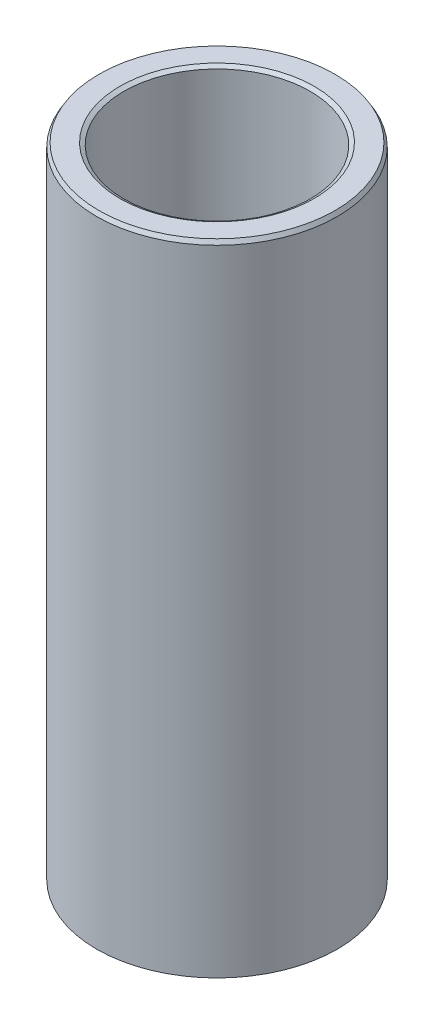
SolidWorks part; units mm, degrees
ref_plane "Front Plane" through (0, 0, 0) normal (0, 0, 1) x (1, 0, 0)
ref_plane "Top Plane" through (0, 0, 0) normal (0, 1, 0) x (1, 0, 0)
ref_plane "Right Plane" through (0, 0, 0) normal (1, 0, 0) x (0, 0, -1)
sketch "Sketch1" plane through (0, 0, 0) normal (0, 1, 0) x (1, 0, 0)
  circle A0 centre (0, 0) radius 15
  dimension "SLEEVE_OD" = 30
extrude "Boss-Extrude1" add sketch "Sketch1" along normal blind 79.846
sketch "Sketch2" plane through (0, 0, 0) normal (0, 1, 0) x (1, 0, 0)
  circle A0 centre (0, 0) radius 11.6153
  dimension "BORE_D" = 23.2305
extrude "Cut-Extrude1" cut sketch "Sketch2" along normal through all
chamfer "Chamfer1" distance 0.4986 angle 30.202 4 edges at (0, 79.846, 11.6153) (0, 0, 11.6153) (0, 0, 15) (0, 79.846, 15) first distance on face at (0, 79.846, 11.6153) first distance on face at (0, 0, 11.6153) first distance on face at (0, 79.846, 15)
